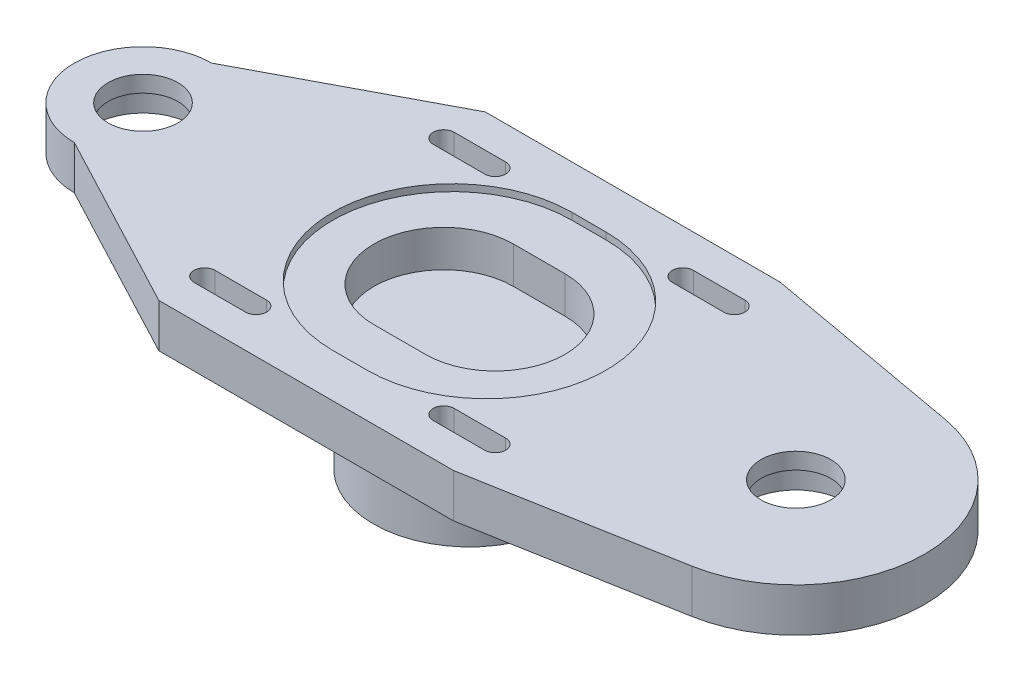
SolidWorks part; units mm, degrees
ref_plane "Front Plane" through (0, 0, 0) normal (0, 0, 1) x (1, 0, 0)
ref_plane "Top Plane" through (0, 0, 0) normal (0, 1, 0) x (1, 0, 0)
ref_plane "Right Plane" through (0, 0, 0) normal (1, 0, 0) x (0, 0, -1)
sketch "Sketch1" plane through (0, 0, 0) normal (0, 1, 0) x (1, 0, 0)
  line L0 (-95, 0) -> (0, 0) construction
  line L1 (-34.8, 34.8) -> (34.8, 34.8) construction
  line L2 (-34.8, 34.8) -> (-34.8, -34.8) construction
  line L3 (-34.8, -34.8) -> (34.8, -34.8) construction
  line L4 (34.8, 34.8) -> (34.8, -34.8) construction
  line L5 (-34.8, 34.8) -> (34.8, -34.8) construction
  line L6 (-34.8, -34.8) -> (34.8, 34.8) construction
  line L7 (-42.9, 47.5) -> (42.9, 47.5)
  line L8 (-42.9, 47.5) -> (-42.9, -47.5) construction
  line L9 (-42.9, -47.5) -> (42.9, -47.5)
  line L10 (42.9, 47.5) -> (42.9, -47.5) construction
  line L11 (-42.9, 47.5) -> (42.9, -47.5) construction
  line L12 (-42.9, -47.5) -> (42.9, 47.5) construction
  line L13 (0, 0) -> (95, 0) construction
  line L14 (-42.3, 34.8) -> (-27.3, 34.8) construction
  line L15 (-42.3, 37.85) -> (-27.3, 37.85)
  line L16 (-42.3, 31.75) -> (-27.3, 31.75)
  line L17 (42.3, 34.8) -> (27.3, 34.8) construction
  line L18 (42.3, 31.75) -> (27.3, 31.75)
  line L19 (42.3, 37.85) -> (27.3, 37.85)
  line L20 (42.3, -34.8) -> (27.3, -34.8) construction
  line L21 (42.3, -37.85) -> (27.3, -37.85)
  line L22 (42.3, -31.75) -> (27.3, -31.75)
  line L23 (-42.3, -34.8) -> (-27.3, -34.8) construction
  line L24 (-42.3, -31.75) -> (-27.3, -31.75)
  line L25 (-42.3, -37.85) -> (-27.3, -37.85)
  line L26 (-8, 0) -> (8, 0) construction
  line L27 (-8, 7.5) -> (8, 7.5)
  line L28 (-8, -7.5) -> (8, -7.5)
  line L29 (-42.9, 47.5) -> (-95, 20)
  line L31 (-95, -20) -> (-42.9, -47.5)
  line L32 (42.9, 47.5) -> (101.655, 36.9048)
  line L34 (101.655, -36.9048) -> (42.9, -47.5)
  circle A0 centre (-34.8, 34.8) radius 3.3 construction
  circle A1 centre (34.8, 34.8) radius 3.3 construction
  circle A2 centre (34.8, -34.8) radius 3.3 construction
  circle A3 centre (-34.8, -34.8) radius 3.3 construction
  circle A5 centre (-95, 0) radius 10.16
  circle A6 centre (-95, 0) radius 14.2875 construction
  arc A9 (-42.3, 37.85) -> (-42.3, 31.75) centre (-42.3, 34.8) ccw
  arc A10 (-27.3, 31.75) -> (-27.3, 37.85) centre (-27.3, 34.8) ccw
  arc A11 (42.3, 31.75) -> (42.3, 37.85) centre (42.3, 34.8) ccw
  arc A12 (27.3, 37.85) -> (27.3, 31.75) centre (27.3, 34.8) ccw
  arc A13 (42.3, -37.85) -> (42.3, -31.75) centre (42.3, -34.8) ccw
  arc A14 (27.3, -31.75) -> (27.3, -37.85) centre (27.3, -34.8) ccw
  arc A15 (-42.3, -31.75) -> (-42.3, -37.85) centre (-42.3, -34.8) ccw
  arc A16 (-27.3, -37.85) -> (-27.3, -31.75) centre (-27.3, -34.8) ccw
  arc A18 (-8, 7.5) -> (-8, -7.5) centre (-8, 0) ccw
  arc A19 (8, -7.5) -> (8, 7.5) centre (8, 0) ccw
  circle A20 centre (95, 0) radius 10.16
  circle A21 centre (95, 0) radius 14.2875 construction
  arc A22 (-95, 20) -> (-95, -20) centre (-95, 0) ccw
  circle A24 centre (95, 0) radius 29.21 construction
  arc A25 (101.655, -36.9048) -> (101.655, 36.9048) centre (95, 0) ccw
  point P0 (0, 0)
  point P18 (-34.8, 34.8)
  point P28 (34.8, 34.8)
  point P36 (34.8, -34.8)
  point P42 (-34.8, -34.8)
  point P49 (0, 0)
  point P61 (132.4451, -39.0015)
  point P63 (95, 37.85)
  dimension "D2" = 6.6
  dimension "D3" = 15
  dimension "D6" = 20.32
  dimension "D7" = 28.575
  dimension "D8" = 6.1
  dimension "D9" = 15
  dimension "D10" = 16
  dimension "D11" = 190
  dimension "D12" = 20
  dimension "D13" = 75
  dimension "D14" = 58.42
  dimension "D1" = 69.6
  dimension "D4" = 85.8
  dimension "D5" = 95
extrude "Boss-Extrude1" add sketch "Sketch1" along normal blind 12.7 contours L9 L8 A5 | L10 L7 L8 L9 A3 A2 A1 A0 region at (0, 0, -44.8489)
sketch "Sketch2" plane through (0, 0, 0) normal (0, 1, 0) x (1, 0, 0)
  circle A0 centre (-95, 0) radius 14.2875
  circle A1 centre (95, 0) radius 14.2875
  dimension "D1" = 28.575
extrude "Cut-Extrude1" cut sketch "Sketch2" along normal blind 7.9375
sketch "Sketch3" plane through (0, 0, 0) normal (0, 1, 0) x (1, 0, 0)
  line L0 (-40.8, 34.8) -> (-28.8, 34.8) construction
  line L1 (-34.8, 34.8) -> (34.8, 34.8) construction
  line L2 (-34.8, 34.8) -> (-34.8, -34.8) construction
  line L3 (-34.8, -34.8) -> (34.8, -34.8) construction
  line L4 (34.8, 34.8) -> (34.8, -34.8) construction
  line L5 (-34.8, 34.8) -> (34.8, -34.8) construction
  line L6 (-34.8, -34.8) -> (34.8, 34.8) construction
  line L7 (-40.8, 40.05) -> (-28.8, 40.05)
  line L8 (-40.8, 29.55) -> (-28.8, 29.55)
  line L9 (40.8, 34.8) -> (28.8, 34.8) construction
  line L10 (40.8, 29.55) -> (28.8, 29.55)
  line L11 (40.8, 40.05) -> (28.8, 40.05)
  line L12 (40.8, -34.8) -> (28.8, -34.8) construction
  line L13 (40.8, -40.05) -> (28.8, -40.05)
  line L14 (40.8, -29.55) -> (28.8, -29.55)
  line L15 (-40.8, -34.8) -> (-28.8, -34.8) construction
  line L16 (-40.8, -29.55) -> (-28.8, -29.55)
  line L17 (-40.8, -40.05) -> (-28.8, -40.05)
  line L19 (-35.0265, 34.8) -> (-37.9132, 39.8) construction
  line L20 (-37.9132, 39.8) -> (-43.6868, 39.8) construction
  line L21 (-43.6868, 39.8) -> (-46.5735, 34.8) construction
  line L22 (-46.5735, 34.8) -> (-43.6868, 29.8) construction
  line L23 (-43.6868, 29.8) -> (-37.9132, 29.8) construction
  line L24 (-37.9132, 29.8) -> (-35.0265, 34.8) construction
  arc A0 (-40.8, 40.05) -> (-40.8, 29.55) centre (-40.8, 34.8) ccw
  arc A1 (-28.8, 29.55) -> (-28.8, 40.05) centre (-28.8, 34.8) ccw
  arc A2 (40.8, 29.55) -> (40.8, 40.05) centre (40.8, 34.8) ccw
  arc A3 (28.8, 40.05) -> (28.8, 29.55) centre (28.8, 34.8) ccw
  arc A4 (40.8, -40.05) -> (40.8, -29.55) centre (40.8, -34.8) ccw
  arc A5 (28.8, -29.55) -> (28.8, -40.05) centre (28.8, -34.8) ccw
  arc A6 (-40.8, -29.55) -> (-40.8, -40.05) centre (-40.8, -34.8) ccw
  arc A7 (-28.8, -40.05) -> (-28.8, -29.55) centre (-28.8, -34.8) ccw
  circle A8 centre (-40.8, 34.8) radius 5 construction
  point P0 (0, 0)
  point P8 (-34.8, 34.8)
  point P14 (34.8, 34.8)
  point P22 (34.8, -34.8)
  point P28 (-34.8, -34.8)
  dimension "D3" = 10
  dimension "D1" = 10.5
  dimension "D2" = 12
  dimension "D4" = 69.6
extrude "Cut-Extrude2" cut sketch "Sketch3" along normal blind 5 contours L17 A7 L16 A6 | L14 A5 L13 A4 | L11 A3 L10 A2 | A1 L7 A0 L8 region at (34.8, 0, -34.8) region at (34.8, 0, 34.8) region at (-34.8, 0, 34.8)
sketch "Sketch4" plane through (0, 0, 0) normal (0, 1, 0) x (1, 0, 0)
  line L0 (-5, 0) -> (5, 0) construction
  line L1 (-5, 34.8) -> (5, 34.8)
  line L2 (-5, -34.8) -> (5, -34.8)
  arc A0 (-5, 34.8) -> (-5, -34.8) centre (-5, 0) ccw
  arc A1 (5, -34.8) -> (5, 34.8) centre (5, 0) ccw
  point P2 (0, 0)
  dimension "D1" = 10
  dimension "D2" = 69.6
extrude "Cut-Extrude3" cut sketch "Sketch4" against normal blind 2 from surface starting at face at (-95, 12.7, 10.16)
sketch "Sketch5" plane through (0, 0, 0) normal (0, 1, 0) x (1, 0, 0)
  line L0 (-7.5, 0) -> (7.5, 0) construction
  line L1 (-7.5, 20.32) -> (7.5, 20.32)
  line L2 (-7.5, -20.32) -> (7.5, -20.32)
  circle A0 centre (0, 0) radius 20.32 construction
  arc A1 (-7.5, 20.32) -> (-7.5, -20.32) centre (-7.5, 0) ccw
  arc A2 (7.5, -20.32) -> (7.5, 20.32) centre (7.5, 0) ccw
  point P5 (0, 0)
  dimension "D1" = 40.64
  dimension "D2" = 15
  dimension "D3" = 40.64
extrude "Cut-Extrude4" cut sketch "Sketch5" against normal blind 12 and the other way blind 22
sketch "Sketch6" plane through (0, 0, 0) normal (0, 1, 0) x (1, 0, 0)
  circle A0 centre (0, 0) radius 27.94
  dimension "D1" = 55.88
extrude "Boss-Extrude2" add sketch "Sketch6" against normal blind 32
